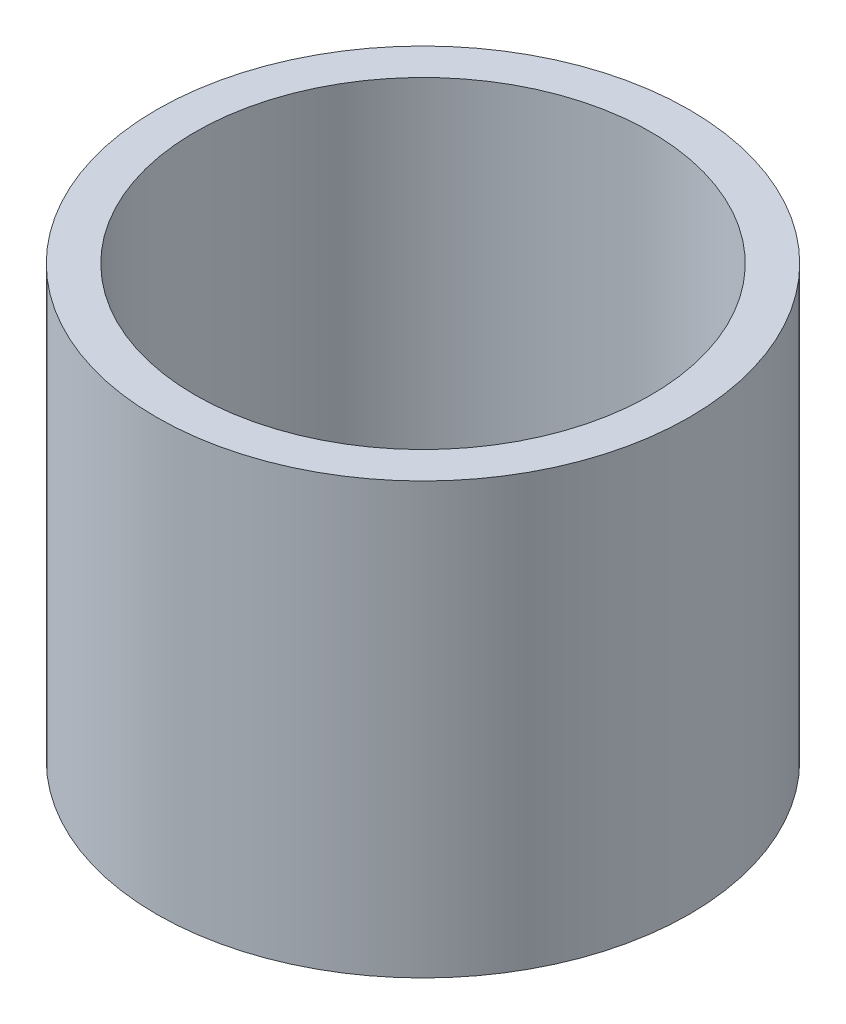
SolidWorks part; units mm, degrees
ref_plane "Front Plane" through (0, 0, 0) normal (0, 0, 1) x (1, 0, 0)
ref_plane "Top Plane" through (0, 0, 0) normal (0, 1, 0) x (1, 0, 0)
ref_plane "Right Plane" through (0, 0, 0) normal (1, 0, 0) x (0, 0, -1)
sketch "Sketch1" plane through (0, 0, 0) normal (0, 1, 0) x (1, 0, 0)
  circle A0 centre (0, 0) radius 25
  dimension "SLEEVE_OD" = 50
extrude "Boss-Extrude1" add sketch "Sketch1" along normal blind 40.3894
sketch "Sketch2" plane through (0, 0, 0) normal (0, 1, 0) x (1, 0, 0)
  circle A0 centre (0, 0) radius 21.3843
  dimension "BORE_D" = 42.7687
extrude "Cut-Extrude1" cut sketch "Sketch2" along normal through all
chamfer "Chamfer1" distance 2.8208 angle 69.792 rebuild error yes
